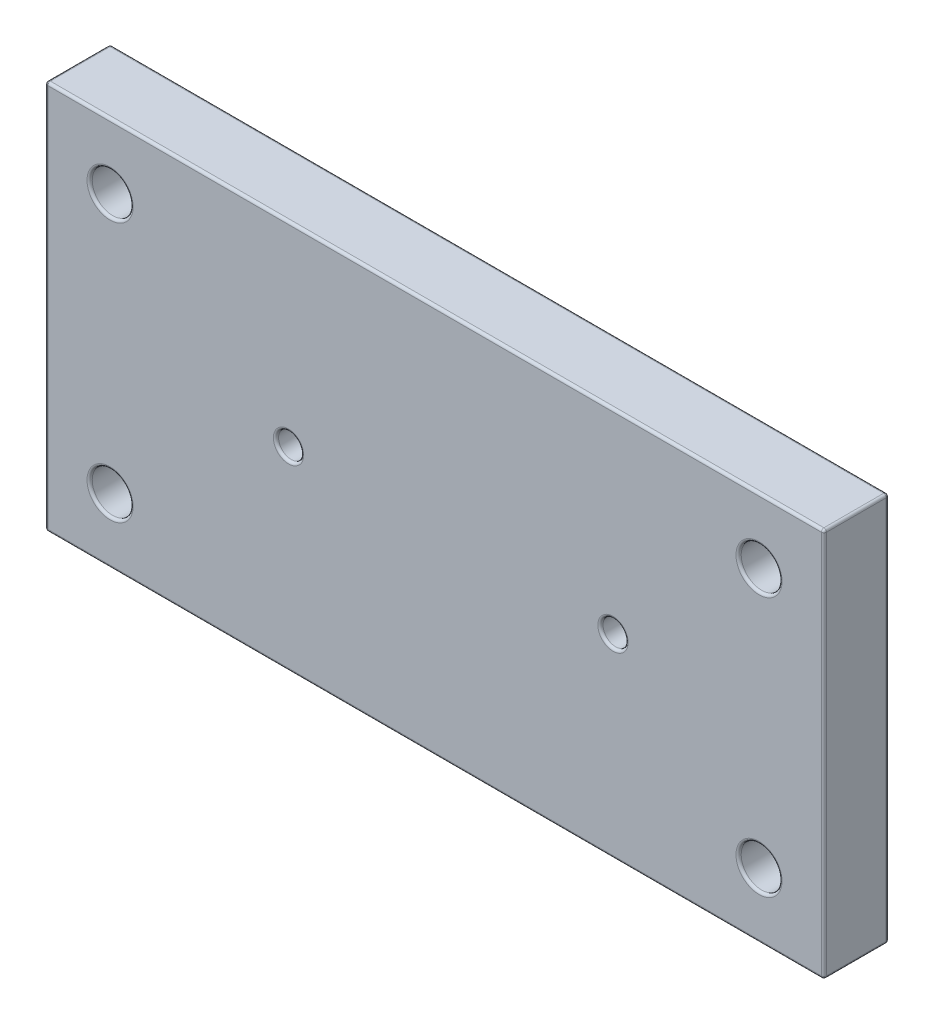
SolidWorks part; units mm, degrees
ref_plane "Front Plane" through (0, 0, 0) normal (0, 0, 1) x (1, 0, 0)
ref_plane "Top Plane" through (0, 0, 0) normal (0, 1, 0) x (1, 0, 0)
ref_plane "Right Plane" through (0, 0, 0) normal (1, 0, 0) x (0, 0, -1)
sketch "Sketch1" plane through (0, 0, 0) normal (0, 0, 1) x (1, 0, 0)
  line L1 (0, 0) -> (152.4, 0)
  line L2 (0, 0) -> (0, 76.2)
  line L3 (0, 76.2) -> (152.4, 76.2)
  line L4 (152.4, 0) -> (152.4, 76.2)
  dimension "D1" = 152.4
  dimension "D2" = 76.2
extrude "Extrude1" add sketch "Sketch1" along normal blind 12.7
hole_wizard "Ø8.0 (8) Diameter Hole1" positions "3DSketch1" profile "Sketch2" hole size "Ø8.0" standard "Ansi Metric" end condition up to next
sketch3d "3DSketch1"
  line L0 (152.4, 76.2, 12.7) -> (0, 76.2, 12.7) construction
  line L1 (0, 76.2, 12.7) -> (0, 0, 12.7) construction
  line L2 (152.4, 0, 12.7) -> (152.4, 76.2, 12.7) construction
  line L3 (0, 0, 12.7) -> (152.4, 0, 12.7) construction
  point P0 (139.7, 63.5, 12.7)
  point P2 (139.7, 12.7, 12.7)
  point P4 (12.7, 12.7, 12.7)
  point P6 (12.7, 63.5, 12.7)
  dimension "D1" = 12.7
  dimension "D2" = 12.7
  dimension "D3" = 12.7
  dimension "D4" = 12.7
  dimension "D5" = 12.7
  dimension "D6" = 12.7
  dimension "D7" = 12.7
  dimension "D8" = 12.7
sketch "Sketch2" plane through (139.7, 63.5, 12.7) normal (1, 0, 0) x (0, -1, 0)
  line L0 (0, 0) -> (0, 12.7)
  line L1 (0, 12.7) -> (4, 12.7)
  line L2 (4, 12.7) -> (4, 0)
  line L5 (4, 0) -> (0, 0)
  line L11 (0, -6.35) -> (0, 107.95) construction
  dimension "Thru Hole Dia." = 8
  dimension "Thru Hole Depth" = 12.7
hole_wizard "#10 (0.1935) Diameter Hole1" positions "3DSketch3" profile "Sketch4" hole size "#10" standard "Ansi Inch" end condition up to next
sketch3d "3DSketch3"
  line L0 (0, 0, 12.7) -> (152.4, 0, 12.7) construction
  line L1 (0, 76.2, 12.7) -> (0, 0, 12.7) construction
  point P0 (47.625, 38.1, 12.7)
  point P2 (111.125, 38.1, 12.7)
  dimension "D1" = 63.5
  dimension "D2" = 38.1
  dimension "D3" = 38.1
  dimension "D4" = 47.625
sketch "Sketch4" plane through (47.625, 38.1, 12.7) normal (1, 0, 0) x (0, -1, 0)
  line L0 (0, 0) -> (0, 12.7)
  line L1 (0, 12.7) -> (2.4574, 12.7)
  line L2 (2.4574, 12.7) -> (2.4574, 0)
  line L5 (2.4574, 0) -> (0, 0)
  line L11 (0, -6.35) -> (0, 107.95) construction
  dimension "Thru Hole Dia." = 4.9149
  dimension "Thru Hole Depth" = 12.7
fillet "Fillet1" radius 0.508 24 edges at (152.4, 0, 6.35) (152.4, 76.2, 6.35) (0, 76.2, 6.35) (0, 0, 6.35) (76.2, 0, 0) (152.4, 38.1, 0) (76.2, 76.2, 0) (0, 38.1, 0) (8.7, 63.5, 0) (8.7, 12.7, 0) (135.7, 12.7, 0) (135.7, 63.5, 0) (143.7, 63.5, 12.7) (143.7, 12.7, 12.7) (76.2, 76.2, 12.7) (152.4, 38.1, 12.7) (76.2, 0, 12.7) (0, 38.1, 12.7) (16.7, 63.5, 12.7) (16.7, 12.7, 12.7) (108.6676, 38.1, 0) (45.1676, 38.1, 0) (113.5824, 38.1, 12.7) (50.0824, 38.1, 12.7)
